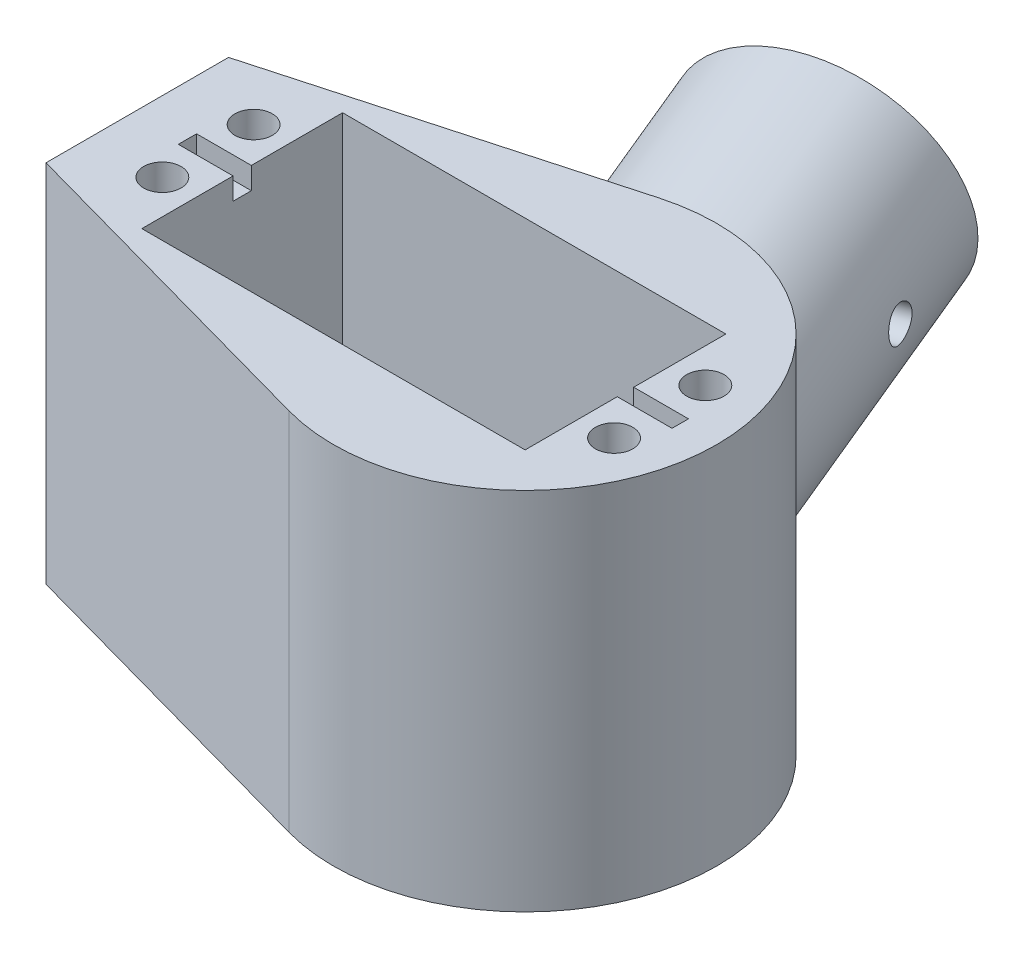
SolidWorks part; units mm, degrees
material "ABS"
ref_plane "Front" through (0, 0, 0) normal (0, 0, 1) x (1, 0, 0)
ref_plane "Top" through (0, 0, 0) normal (0, 1, 0) x (1, 0, 0)
ref_plane "Right" through (0, 0, 0) normal (1, 0, 0) x (0, 0, -1)
sketch "Sketch1" plane through (0, 0, 0) normal (0, 1, 0) x (1, 0, 0)
  line L0 (-10.25, 0) -> (17, 0) construction
  line L1 (-37.5, -10) -> (17, -10)
  line L2 (-37.5, -10) -> (-37.5, 10)
  line L3 (-37.5, 10) -> (17, 10)
  line L4 (17, -10) -> (17, 10)
  line L5 (-37.5, -10) -> (17, 10) construction
  line L6 (-37.5, 10) -> (17, -10) construction
  line L7 (-42.5, -10) -> (-42.5, 10)
  line L8 (-30.25, -10) -> (9.75, -10)
  line L9 (-30.25, -10) -> (-30.25, 10)
  line L10 (-30.25, 10) -> (9.75, 10)
  line L11 (9.75, -10) -> (9.75, 10)
  line L12 (-30.25, -10) -> (9.75, 10) construction
  line L13 (-30.25, 10) -> (9.75, -10) construction
  line L14 (-42.5, 10) -> (-5.6152, 20.2354)
  line L15 (-42.5, -10) -> (-5.6152, -20.2354)
  line L16 (-42.5, 0) -> (-39.8632, 0) construction
  circle A0 centre (0, 0) radius 21
  circle A1 centre (0, 0) radius 6
  point P3 (-10.25, 0)
  dimension "D1" = 42
  dimension "D4" = 12
  dimension "D2" = 20
  dimension "D3" = 54.5
  dimension "D5" = 37.5
  dimension "D6" = 20
  dimension "D7" = 40
  dimension "D8" = 5
  dimension "D9" = 10
extrude "Boss-Extrude1" add sketch "Sketch1" along normal blind 40 contours A0 L14 L7 L15 L1 L2 L3 | L1 L9 L3 L2 | L10 A0 L8 L11 A1 | A0 L3 L9 L1 | A0 L10 L3 L4 L1 L8 | L11 L1 L4 L3 region at (-33.875, 0, 0) region at (-33.875, 0, 10.5476) region at (-25.1857, 0, 0) region at (-6.4396, 0, 0) region at (-4.3581, 0, 10.5763) region at (13.375, 0, 0)
sketch "Sketch2" plane through (0, 40, 0) normal (0, 1, 0) x (1, 0, 0)
  line L1 (-31, -11) -> (11, -11)
  line L2 (-31, -11) -> (-31, 11)
  line L3 (-31, 11) -> (11, 11)
  line L4 (11, -11) -> (11, 11)
  line L5 (-31, -11) -> (11, 11) construction
  line L6 (-31, 11) -> (11, -11) construction
  point P0 (-10, 0)
  dimension "D1" = 22
  dimension "D2" = 42
  dimension "D3" = 10
extrude "Cut-Extrude1" cut sketch "Sketch2" against normal blind 25
sketch "Sketch3" plane through (0, 40, 0) normal (0, 1, 0) x (1, 0, 0)
  circle A0 centre (14.75, 5) radius 2.05
  circle A1 centre (14.75, -5) radius 2.05
  circle A2 centre (-34.75, 5) radius 2.05
  circle A3 centre (-34.75, -5) radius 2.05
  dimension "D1" = 10
  dimension "D3" = 4.1
  dimension "D4" = 4.1
  dimension "D2" = 5
  dimension "D6" = 34.75
  dimension "D5" = 2
extrude "Cut-Extrude2" cut sketch "Sketch3" against normal blind 12
sketch "Sketch4" plane through (0, 15, 0) normal (0, 1, 0) x (1, 0, 0)
  circle A0 centre (0, 0) radius 9.55
  dimension "D1" = 19.1
extrude "Cut-Extrude3" cut sketch "Sketch4" against normal blind 5
sketch "Sketch5" plane through (0, 0, 0) normal (0, -1, 0) x (1, 0, 0)
  circle A0 centre (0, 0) radius 9.55
  dimension "D1" = 19.1
extrude "Cut-Extrude4" cut sketch "Sketch5" against normal blind 6
sketch "Sketch7" plane through (0, 40, 0) normal (0, 1, 0) x (1, 0, 0)
  line L0 (-31, 11) -> (-31, -11) construction
  line L1 (-37, -1) -> (-25, -1)
  line L2 (-37, -1) -> (-37, 1)
  line L3 (-37, 1) -> (-25, 1)
  line L4 (-25, -1) -> (-25, 1)
  line L5 (-37, -1) -> (-25, 1) construction
  line L6 (-37, 1) -> (-25, -1) construction
  line L7 (11, -11) -> (11, 11) construction
  line L8 (5, -0.9) -> (17, -0.9)
  line L9 (5, -0.9) -> (5, 0.9)
  line L10 (5, 0.9) -> (17, 0.9)
  line L11 (17, -0.9) -> (17, 0.9)
  line L12 (5, -0.9) -> (17, 0.9) construction
  line L13 (5, 0.9) -> (17, -0.9) construction
  line L14 (-31, 11) -> (-31, -11) construction
  line L15 (11, -11) -> (11, 11) construction
  line L16 (-31, 11) -> (-31, -11)
  line L17 (11, -11) -> (11, 11)
  point P0 (-31, 0)
  point P7 (11, 0)
  line M9 (11, 11) -> (11, -11)
  line M11 (-31, -11) -> (-31, 11)
  dimension "D1" = 2
  dimension "D2" = 12
  dimension "D3" = 12
  dimension "D4" = 1.8
extrude "Cut-Extrude5" cut sketch "Sketch7" against normal blind 2.4 contours L3 L2 L1 M11 | L8 L11 L10 M9 region at (-34, 40, 0) region at (14, 40, 0)
ref_plane "Plane5" through (0, 34, 0) normal (0, 1, 0) x (1, 0, 0)
ref_plane "Plane6" through (0, 20, 0) normal (0, 1, 0) x (1, 0, 0)
ref_axis "Axis3" through (0, 20, -80.9) along (0, 0, 1)
ref_plane "Plane10" through (-3.4202, 19.3969, 0) normal (0.1736, -0.9848, 0) x (0, 0, 1)
ref_axis "Axis4" through (7.9671, 21.4048, 0) along (-0.9848, -0.1736, 0)
ref_plane "Plane11" through (-0.2002, 1.1352, -4.6234) normal (0.042, -0.2382, 0.9703) x (-0.9848, -0.1736, 0)
ref_plane "Plane12" through (3.4202, 0.6031, 0) normal (0.9848, 0.1736, 0) x (0, 0, 1)
ref_axis "Axis5" through (31.4873, -158.5731, -45.2101) along (-0.1685, 0.9556, 0.2419)
ref_plane "Plane13" through (-1.0555, 0.7156, -3.5618) normal (0.279, -0.1892, 0.9415) x (-0.1685, 0.9556, 0.2419)
ref_plane "Plane14" through (-14.4479, 9.7953, -48.7525) normal (0.279, -0.1892, 0.9415) x (-0.1685, 0.9556, 0.2419)
sketch "Sketch10" plane through (-14.4479, 9.7953, -48.7525) normal (0.279, -0.1892, 0.9415) x (-0.1685, 0.9556, 0.2419)
  line L0 (34.2729, -8.4865) -> (-3.9493, 0.5586) construction
  circle A0 centre (15.1618, -3.9639) radius 10
  circle A1 centre (15.1618, -3.9639) radius 13.5
  dimension "D1" = 20
  dimension "D2" = 27
extrude "Boss-Extrude3" add sketch "Sketch10" along normal up to next
ref_plane "Plane15" through (-7.4727, 5.0663, -25.2157) normal (-0.279, 0.1892, -0.9415) x (-0.9603, -0.055, 0.2735)
sketch "Sketch11" plane through (-7.4727, 5.0663, -25.2157) normal (-0.279, 0.1892, -0.9415) x (-0.9603, -0.055, 0.2735)
  circle A0 centre (-1.2422, 15.6221) radius 10 construction
  circle A1 centre (-1.2422, 15.6221) radius 10
extrude "Boss-Extrude4" add sketch "Sketch11" against normal up to next
ref_axis "Axis6" through (-4.4411, 19.204, -16.2734) along (-0.279, 0.1892, -0.9415)
ref_plane "Plane18" through (0, 15.316, 3.0773) normal (0, -0.9804, -0.197) x (-0.279, 0.1892, -0.9415)
ref_plane "Plane19" through (1.1928, 0.0683, -0.3398) normal (-0.9603, -0.055, 0.2735) x (-0.279, 0.1892, -0.9415)
sketch "Sketch15" plane through (1.1928, 0.0683, -0.3398) normal (-0.9603, -0.055, 0.2735) x (-0.279, 0.1892, -0.9415)
  line L0 (51.7832, -15.6221) -> (39.2832, -15.6221) construction
  line L1 (51.7832, -29.1221) -> (51.7832, -2.1221) construction
  circle A0 centre (39.2832, -15.6221) radius 1.85
  dimension "D2" = 3.7
  dimension "D1" = 12.5
extrude "Cut-Extrude8" cut sketch "Sketch15" against normal mid plane 27
